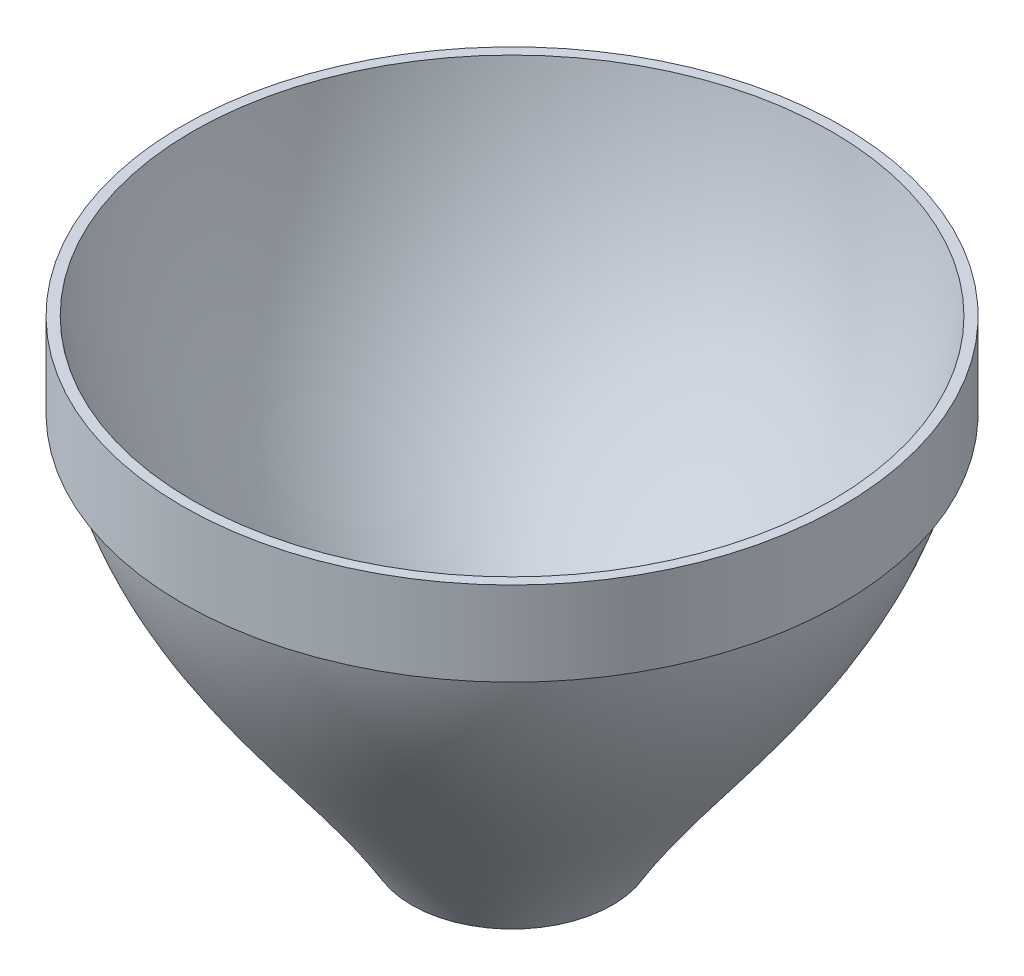
SolidWorks part; units mm, degrees
ref_plane "Płaszczyzna przednia" through (0, 0, 0) normal (0, 0, 1) x (1, 0, 0)
ref_plane "Płaszczyzna górna" through (0, 0, 0) normal (0, 1, 0) x (1, 0, 0)
ref_plane "Płaszczyzna prawa" through (0, 0, 0) normal (1, 0, 0) x (0, 0, -1)
sketch "Sketch1" plane through (0, 0, 0) normal (0, 0, 1) x (1, 0, 0)
  line L15 (24.8342, 148.4714) -> (24.8342, -40.5547) construction
  line L26 (18.8342, 99.1874) -> (16.8342, 99.1874)
  line L30 (-0.6464, 129.1655) -> (-1.4464, 129.1655)
  line L32 (-0.6464, 135.8755) -> (-1.4464, 135.8755)
  line L33 (-1.4464, 135.8755) -> (-1.4464, 129.1655)
  spline S0 degree 3 poles (-0.6464, 135.8755) (2.3951, 117.2827) (12.0104, 111.5519) (18.8342, 99.1874) knots 0 0 0 0 1 1 1 1
  spline S2 degree 3 poles (-0.6464, 129.1655) (-0.4981, 128.4101) (-0.1372, 126.9041) (0.7948, 124.0115) (2.9236, 119.1806) (6.1828, 114.1346) (9.688, 109.3827) (12.2998, 105.9249) (14.342, 103.1046) (15.8313, 100.8586) (16.5067, 99.7534) (16.8342, 99.1874) knots 0.117145 0.117145 0.117145 0.117145 0.169312 0.221479 0.325814 0.534482 0.638817 0.743151 0.847485 0.899652 0.95182 0.95182 0.95182 0.95182
  point P1 (0, 0)
  point P2 (0, 0)
  point P3 (0, 0)
  point P5 (16.4003, 99.1874)
  dimension "D1" = 6.71
  dimension "D2" = 0.8
  dimension "D3" = 2
  dimension "D7" = 6
revolve "Revolve1" add sketch "Sketch1" angle 360 about L15 region at (17.8342, 99.6066, 0)
equation "\"outerdiameter\"= 30"
equation "\"wallthick\"= 2"
